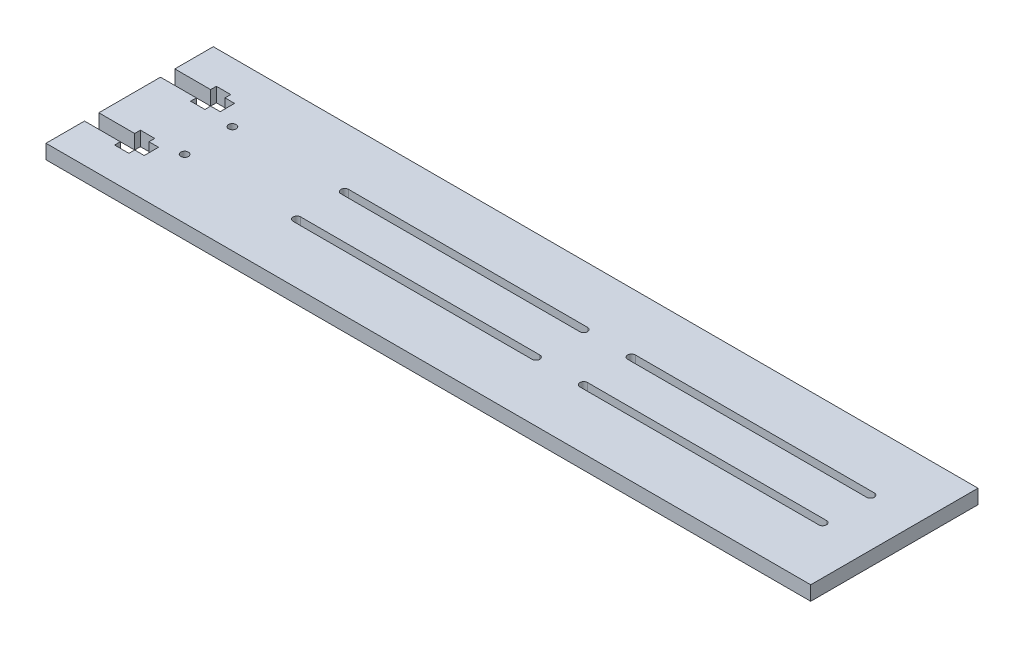
SolidWorks part; units mm, degrees
ref_plane "Front Plane" through (0, 0, 0) normal (0, 0, 1) x (1, 0, 0)
ref_plane "Top Plane" through (0, 0, 0) normal (0, 1, 0) x (1, 0, 0)
ref_plane "Right Plane" through (0, 0, 0) normal (1, 0, 0) x (0, 0, -1)
sketch "Sketch1" plane through (0, 0, 0) normal (0, 1, 0) x (1, 0, 0)
  line L1 (-160, -35) -> (160, -35)
  line L2 (-160, -35) -> (-160, 35)
  line L3 (-160, 35) -> (160, 35)
  line L4 (160, -35) -> (160, 35)
  line L5 (-160, -35) -> (160, 35) construction
  line L6 (-160, 35) -> (160, -35) construction
  point P0 (0, 0)
  dimension "D1" = 320
  dimension "D2" = 70
extrude "Boss-Extrude1" add sketch "Sketch1" along normal blind 6
sketch "Sketch3" plane through (0, 6, 0) normal (0, 1, 0) x (1, 0, 0)
  line L0 (-160, 0) -> (-135, 0) construction
  line L1 (-160, 35) -> (-160, -35) construction
  line L2 (-160, 15.9) -> (-135, 15.9) construction
  line L7 (-160, 12.9) -> (-145, 12.9)
  line L8 (-160, 18.9) -> (-145, 18.9)
  line L9 (-160, 12.9) -> (-160, 18.9)
  line L10 (-135, 12.9) -> (-135, 18.9)
  line L18 (-145, 10.5) -> (-139, 10.5)
  line L19 (-145, 10.5) -> (-145, 12.9)
  line L20 (-145, 21.3) -> (-139, 21.3)
  line L21 (-139, 10.5) -> (-139, 12.9)
  line L22 (-145, 10.5) -> (-139, 21.3) construction
  line L23 (-145, 21.3) -> (-139, 10.5) construction
  line L29 (-139, 18.9) -> (-139, 21.3)
  line L30 (-139, 18.9) -> (-135, 18.9)
  line L31 (-160, 18.9) -> (-135, 18.9) construction
  line L32 (-139, 12.9) -> (-135, 12.9)
  line L33 (-160, 12.9) -> (-135, 12.9) construction
  line L34 (-145, 18.9) -> (-145, 21.3)
  line L35 (-145, -21.3) -> (-139, -10.5) construction
  line L36 (-145, -10.5) -> (-139, -21.3) construction
  line L37 (-160, -15.9) -> (-135, -15.9) construction
  line L38 (-145, -18.9) -> (-145, -21.3)
  line L39 (-139, -12.9) -> (-135, -12.9)
  line L40 (-139, -18.9) -> (-135, -18.9)
  line L41 (-139, -18.9) -> (-139, -21.3)
  line L42 (-139, -10.5) -> (-139, -12.9)
  line L43 (-145, -21.3) -> (-139, -21.3)
  line L44 (-145, -10.5) -> (-145, -12.9)
  line L45 (-145, -10.5) -> (-139, -10.5)
  line L46 (-135, -12.9) -> (-135, -18.9)
  line L47 (-160, -12.9) -> (-160, -18.9)
  line L48 (-160, -18.9) -> (-145, -18.9)
  line L49 (-160, -12.9) -> (-145, -12.9)
  point P11 (-142, 15.9)
  point P47 (-142, -15.9)
  dimension "D3" = 15
  dimension "D4" = 15.9
  dimension "D7" = 25
  dimension "D1" = 10.8
  dimension "D2" = 6
  dimension "D5" = 3
  dimension "D6" = 3
extrude "Cut-Extrude2" cut sketch "Sketch3" against normal through all
sketch "Sketch5" plane through (0, 6, 0) normal (0, 1, 0) x (1, 0, 0)
  line L0 (40, -10) -> (140, -10) construction
  line L1 (40, -8.4) -> (140, -8.4)
  line L2 (40, -11.6) -> (140, -11.6)
  line L3 (-80, -10) -> (20, -10) construction
  line L4 (-80, -8.4) -> (20, -8.4)
  line L5 (-80, -11.6) -> (20, -11.6)
  line L6 (-80, 10) -> (20, 10) construction
  line L7 (-80, 11.6) -> (20, 11.6)
  line L8 (-80, 8.4) -> (20, 8.4)
  line L9 (40, 10) -> (140, 10) construction
  line L10 (40, 11.6) -> (140, 11.6)
  line L11 (40, 8.4) -> (140, 8.4)
  line L12 (160, -35) -> (160, 35) construction
  line L13 (-160, -35) -> (160, -35) construction
  arc A0 (40, -8.4) -> (40, -11.6) centre (40, -10) ccw
  arc A1 (140, -11.6) -> (140, -8.4) centre (140, -10) ccw
  arc A2 (-80, -8.4) -> (-80, -11.6) centre (-80, -10) ccw
  arc A3 (20, -11.6) -> (20, -8.4) centre (20, -10) ccw
  arc A4 (-80, 11.6) -> (-80, 8.4) centre (-80, 10) ccw
  arc A5 (20, 8.4) -> (20, 11.6) centre (20, 10) ccw
  arc A6 (40, 11.6) -> (40, 8.4) centre (40, 10) ccw
  arc A7 (140, 8.4) -> (140, 11.6) centre (140, 10) ccw
  point P3 (90, -10)
  point P12 (-30, -10)
  point P19 (-30, 10)
  point P26 (90, 10)
  dimension "D2" = 3.2
  dimension "D1" = 100
  dimension "D5" = 20
  dimension "D6" = 25
  dimension "D3" = 2
  dimension "D4" = 2
extrude "Cut-Extrude3" cut sketch "Sketch5" against normal through all
sketch "Sketch6" plane through (0, 0, 0) normal (0, -1, 0) x (1, 0, 0)
  circle A0 centre (-127, -10) radius 1.6 construction
  circle A1 centre (-127, 10) radius 1.6 construction
  circle A2 centre (-127, -10) radius 1.6
  circle A3 centre (-127, 10) radius 1.6
extrude "Cut-Extrude4" cut sketch "Sketch6" against normal through all
